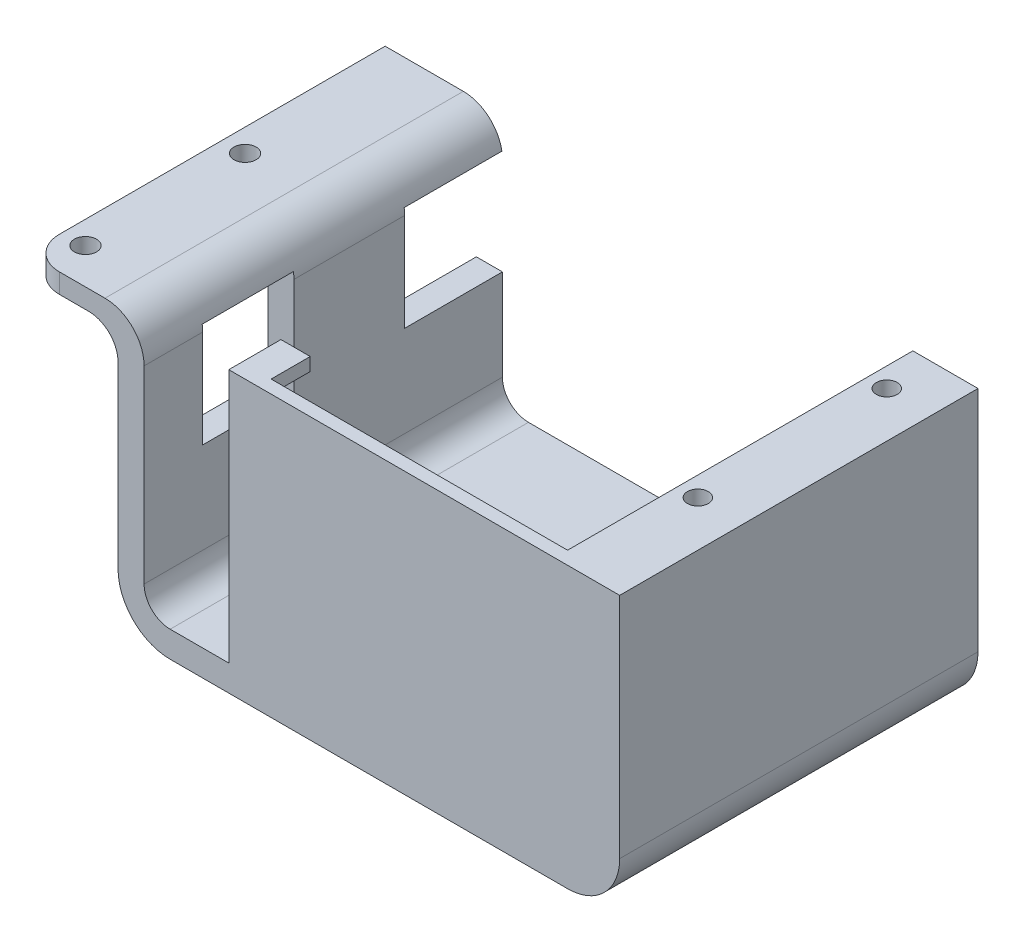
SolidWorks part; units mm, degrees
ref_plane "前视基准面" through (0, 0, 0) normal (0, 0, 1) x (1, 0, 0)
ref_plane "上视基准面" through (0, 0, 0) normal (0, 1, 0) x (1, 0, 0)
ref_plane "右视基准面" through (0, 0, 0) normal (1, 0, 0) x (0, 0, -1)
sketch "草图1" plane through (0, 0, 0) normal (0, 0, 1) x (1, 0, 0)
  line L0 (69, 36) -> (63, 36)
  line L1 (0, 0) -> (69, 0) construction
  line L2 (0, 0) -> (0, 36) construction
  line L3 (0, 36) -> (69, 36) construction
  line L4 (69, 0) -> (69, 36) construction
  line L5 (63, 36) -> (63, 39)
  line L6 (63, 39) -> (73, 39)
  line L7 (73, 39) -> (73, 4)
  line L8 (65, -4) -> (4, -4)
  line L9 (-4, 4) -> (-4, 36)
  line L10 (0, 39) -> (-18, 39)
  line L11 (-18, 39) -> (-18, 36)
  line L12 (-18, 36) -> (-4, 36)
  line L13 (0, 39) -> (0, 4)
  line L14 (4, 0) -> (65, 0)
  line L15 (69, 4) -> (69, 36)
  line L16 (0, 39) -> (63, 39)
  arc A0 (0, 4) -> (4, 0) centre (4, 4) ccw
  arc A1 (65, 0) -> (69, 4) centre (65, 4) ccw
  arc A2 (73, 4) -> (65, -4) centre (65, 4) cw
  arc A3 (4, -4) -> (-4, 4) centre (4, 4) cw
  dimension "D8" = 4
  dimension "D9" = 8
  dimension "D1" = 3
  dimension "D2" = 4
  dimension "D3" = 6
  dimension "D4" = 91
  dimension "D5" = 4
  dimension "D6" = 4
  dimension "D7" = 69
  dimension "D10" = 36
extrude "凸台-拉伸1" add sketch "草图1" along normal blind 54 contours A3 L8 A2 L7 L6 L5 L0 L15 A1 L14 A0 L13 L10 L11 L12 L9 region at (66, 37.0065, 0)
extrude "凸台-拉伸2" add sketch "草图1<3>" against normal blind 2 contours L14 A1 L15 L0 L5 L16 L13 A0 | A3 L8 A2 L7 L6 L5 L0 L15 A1 L14 A0 L13 L10 L11 L12 L9 region at (34.2873, 19.4264, 0) region at (66, 37.0065, 0)
sketch "草图1<3>" plane through (0, 0, 0) normal (0, 0, 1) x (1, 0, 0) same geometry as "草图1"
sketch "草图2" plane through (0, -4, 0) normal (0, -1, 0) x (1, 0, 0)
  line L0 (22, 38) -> (43, 38) construction
  line L1 (65, 54) -> (4, 54) construction
  line L2 (-4, 54) -> (-4, -2) construction
  line L3 (73, 54) -> (73, -2) construction
  line L4 (-18, 54) -> (-18, -2) construction
  line L5 (14.5, 48) -> (29.5, 48) construction
  line L6 (14.5, 48) -> (14.5, 28) construction
  line L7 (14.5, 28) -> (29.5, 28) construction
  line L8 (29.5, 48) -> (29.5, 28) construction
  line L9 (14.5, 48) -> (29.5, 28) construction
  line L10 (14.5, 28) -> (29.5, 48) construction
  line L11 (35.5, 48) -> (50.5, 48) construction
  line L12 (35.5, 48) -> (35.5, 28) construction
  line L13 (35.5, 28) -> (50.5, 28) construction
  line L14 (50.5, 48) -> (50.5, 28) construction
  line L15 (35.5, 48) -> (50.5, 28) construction
  line L16 (35.5, 28) -> (50.5, 48) construction
  line L17 (-18, 46) -> (-4, 46)
  line L18 (-18, 46) -> (-18, 32)
  line L19 (-18, 32) -> (-4, 32)
  line L20 (-4, 46) -> (-4, 32)
  line L21 (-18, 54) -> (-4, 54) construction
  line L22 (-18, -2) -> (-4, -2) construction
  line L23 (-4, -2) -> (-18, -2)
  line L24 (-4, -2) -> (-4, 15)
  line L25 (-4, 15) -> (-18, 15)
  line L26 (-18, -2) -> (-18, 15)
  line L27 (-4, -2) -> (4, -2) construction
  line L29 (73, -2) -> (-18, -2)
  line L30 (73, -2) -> (73, 0)
  line L31 (73, 0) -> (-18, 0)
  line L32 (-18, -2) -> (-18, 0)
  circle A0 centre (-14.5, 25) radius 1.7
  circle A1 centre (-14.5, 49.5) radius 1.7
  circle A2 centre (66, 7) radius 1.6
  circle A3 centre (66, 36) radius 1.6
  line M1 (4, 54) -> (4, -2)
  line M2 (4, -2) -> (65, -2)
  line M3 (65, -2) -> (65, 54)
  dimension "D14" = 3.4
  dimension "D15" = 3.4
  dimension "D17" = 3.2
  dimension "D18" = 3.2
  dimension "D1" = 16
  dimension "D2" = 26
  dimension "D3" = 30
  dimension "D4" = 15
  dimension "D5" = 20
  dimension "D6" = 15
  dimension "D7" = 20
  dimension "D8" = 0
  dimension "D9" = 14
  dimension "D10" = 8
  dimension "D11" = 0
  dimension "D12" = 17
  dimension "D13" = 17
  dimension "D16" = 3.5
  dimension "D19" = 7
  dimension "D20" = 7
  dimension "D21" = 29
  dimension "D22" = 10
  dimension "D23" = 4.5
  dimension "D24" = 51.5
  dimension "D25" = 13.5
extrude "切除-拉伸1" cut sketch "草图2" against normal through all contours A1 | A0 | L24 L31 L26 L23 | L31 L24 L29 M1 | L31 M3 M1 M2 | L30 L31 L29 M3 region at (-11, -4, -1) region at (0, -4, -1) region at (34.5, -4, -1) region at (69, -4, -1) region at (-14.5, -4, 25) region at (-14.5, -4, 49.5)
sketch "草图3" plane through (-4, 0, 0) normal (-1, 0, 0) x (0, 0, 1)
  line L1 (32, 34) -> (46, 34)
  line L2 (32, 34) -> (32, 18)
  line L3 (32, 18) -> (46, 18)
  line L4 (46, 34) -> (46, 18)
  line L5 (0, 34) -> (15, 34)
  line L6 (0, 34) -> (0, 18)
  line L7 (0, 18) -> (15, 18)
  line L8 (15, 34) -> (15, 18)
  line L16 (54, 36) -> (0, 36) construction
  dimension "D1" = 16
  dimension "D2" = 2
extrude "切除-拉伸2" cut sketch "草图3" against normal up to next contours L8 L6 L7 | L4 L2 L3 region at (-4, 26, 39) region at (-4, 26, 7.5)
extrude "切除-拉伸5" cut sketch "草图2<3>" against normal through all from surface contours A3 M3 | A3 M3 | A2 M3 | A2 M3 region at (64.7557, -4, 36) region at (66.1856, -4, 36) region at (64.7557, -4, 7) region at (66.1856, -4, 7) starting at face at (66, 36, 27)
sketch "草图2<3>" plane through (0, -4, 0) normal (0, -1, 0) x (1, 0, 0) same geometry as "草图2"
sketch "草图5" plane through (0, 0, 54) normal (0, 0, 1) x (1, 0, 0)
  line L0 (0, 39) -> (63, 39)
  line L1 (13, 39) -> (13, -4)
  line L12 (4, -4) -> (65, -4)
  line L13 (73, 4) -> (73, 39)
  line L14 (73, 39) -> (63, 39)
  line L15 (63, 39) -> (63, 36)
  line L16 (63, 36) -> (69, 36)
  line L17 (69, 36) -> (69, 4)
  line L18 (65, 0) -> (4, 0)
  line L19 (0, 4) -> (0, 39)
  line L20 (0, 39) -> (-18, 39)
  line L21 (-18, 39) -> (-18, 36)
  line L22 (-18, 36) -> (-4, 36)
  line L23 (-4, 36) -> (-4, 4)
  line L24 (4, -4) -> (65, -4)
  line L25 (73, 4) -> (73, 39)
  line L26 (73, 39) -> (63, 39)
  line L27 (63, 39) -> (63, 36)
  line L28 (63, 36) -> (69, 36)
  line L29 (69, 36) -> (69, 4)
  line L30 (65, 0) -> (4, 0)
  line L31 (0, 4) -> (0, 39)
  line L32 (0, 39) -> (-18, 39)
  line L33 (-18, 39) -> (-18, 36)
  line L34 (-18, 36) -> (-4, 36)
  line L35 (-4, 36) -> (-4, 4)
  arc A4 (-4, 4) -> (4, -4) centre (4, 4) ccw
  arc A5 (65, -4) -> (73, 4) centre (65, 4) ccw
  arc A6 (65, 0) -> (69, 4) centre (65, 4) ccw
  arc A7 (0, 4) -> (4, 0) centre (4, 4) ccw
  arc A8 (-4, 4) -> (4, -4) centre (4, 4) ccw
  arc A9 (65, -4) -> (73, 4) centre (65, 4) ccw
  arc A10 (65, 0) -> (69, 4) centre (65, 4) ccw
  arc A11 (0, 4) -> (4, 0) centre (4, 4) ccw
  arc M17 (-4, 4) -> (4, -4) centre (4, 4) ccw
  line M18 (4, -4) -> (65, -4)
  arc M19 (65, -4) -> (73, 4) centre (65, 4) ccw
  line M20 (73, 4) -> (73, 39)
  line M21 (73, 39) -> (63, 39)
  line M22 (63, 39) -> (63, 36)
  line M23 (63, 36) -> (69, 36)
  line M24 (69, 36) -> (69, 4)
  arc M25 (69, 4) -> (65, 0) centre (65, 4) cw
  line M26 (65, 0) -> (4, 0)
  arc M27 (4, 0) -> (0, 4) centre (4, 4) cw
  line M28 (0, 4) -> (0, 39)
  line M29 (0, 39) -> (-18, 39)
  line M30 (-18, 39) -> (-18, 36)
  line M31 (-18, 36) -> (-4, 36)
  line M32 (-4, 36) -> (-4, 4)
  dimension "D2" = 13
  dimension "D1" = 0
extrude "凸台-拉伸3" add sketch "草图5" along normal blind 1 and the other way blind 1 contours L1 M26 M18 M19 M20 M21 M22 M23 M24 M25 | L0 L1 M26 M25 M24 M23 M22 | L1 M26 M27 M28 M29 M30 M31 M32 M17 M18 region at (-1.6994, 17.6554, 54) region at (40.7489, 19.3797, 54) region at (68, 38.2618, 54)
sketch "草图6" plane through (0, 0, 53) normal (0, 0, -1) x (-1, 0, 0)
  line L1 (-13, 39) -> (-17.5, 39)
  line L2 (-13, 39) -> (-13, 37)
  line L3 (-13, 37) -> (-17.5, 37)
  line L4 (-17.5, 39) -> (-17.5, 37)
  dimension "D1" = 2
  dimension "D2" = 4.5
extrude "凸台-拉伸4" add sketch "草图6" along normal blind 6
fillet "圆角1" radius 4.5 1 edges at (-4, 36, 27.5)
fillet "圆角2" radius 6 1 edges
sketch "草图4" plane through (0, -4, 0) normal (0, -1, 0) x (1, 0, 0)
  line L1 (-66.5935, 87.989) -> (108.6151, 87.989)
  line L2 (-66.5935, 87.989) -> (-66.5935, 6.254)
  line L3 (-66.5935, 6.254) -> (108.6151, 6.254)
  line L4 (108.6151, 87.989) -> (108.6151, 6.254)
  line L5 (-23.7065, 0.8458) -> (79.8549, 0.8458)
  line L6 (-23.7065, 0.8458) -> (-23.7065, -7.359)
  line L7 (-23.7065, -7.359) -> (79.8549, -7.359)
  line L8 (79.8549, 0.8458) -> (79.8549, -7.359)
extrude "切除-拉伸3" [suppressed] cut sketch "草图4" against normal through all
fillet "圆角3" radius 5 1 edges at (-18, 37.5, 55)
